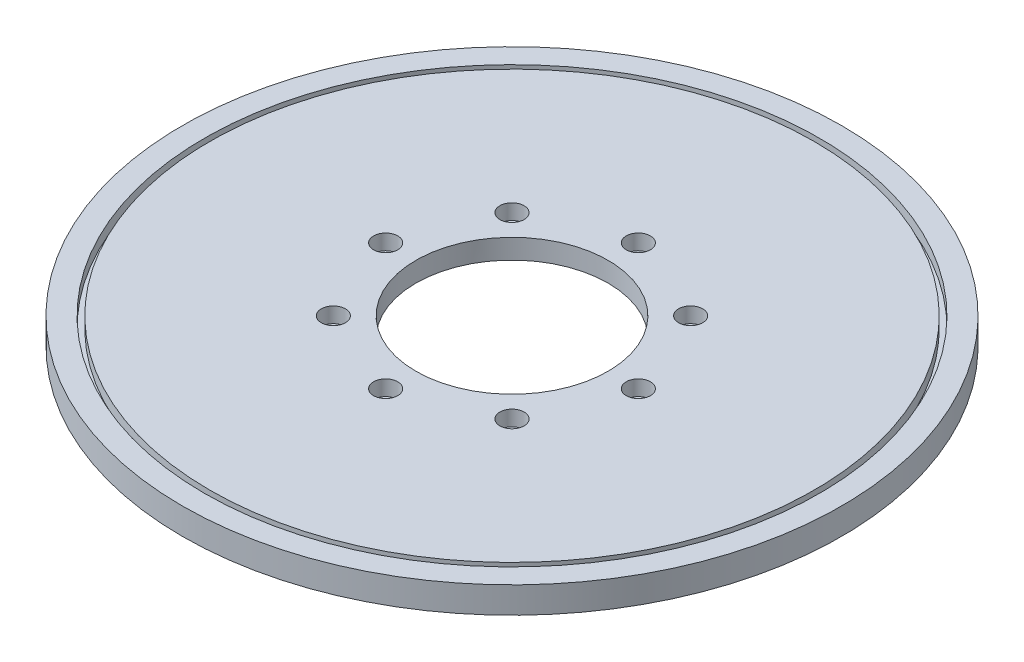
SolidWorks part; units mm, degrees
ref_plane "Front Plane" through (0, 0, 0) normal (0, 0, 1) x (1, 0, 0)
ref_plane "Top Plane" through (0, 0, 0) normal (0, 1, 0) x (1, 0, 0)
ref_plane "Right Plane" through (0, 0, 0) normal (1, 0, 0) x (0, 0, -1)
sketch "Sketch1" plane through (0, 0, 0) normal (0, 1, 0) x (1, 0, 0)
  circle A0 centre (0, 0) radius 300
  point P0 (0, 0)
  dimension "D1" = 600
extrude "plate" add sketch "Sketch1" along normal blind 24
sketch "Sketch2" plane through (0, 24, 0) normal (0, 1, 0) x (1, 0, 0)
  circle A0 centre (0, 0) radius 87.5
  dimension "D1" = 175
extrude "bearing-hole" cut sketch "Sketch2" against normal through all
sketch "Sketch4" plane through (0, 24, 0) normal (0, 1, 0) x (1, 0, 0)
  circle A0 centre (0, 0) radius 280
  circle A1 centre (0, 0) radius 275
  point P0 (0, 0)
  point P6 (0, 0)
  dimension "D1" = 560
  dimension "D2" = 550
extrude "Cut-Extrude3" cut sketch "Sketch4" against normal blind 10
sketch "Sketch5" plane through (0, 0, 0) normal (0, -1, 0) x (1, 0, 0)
  circle A0 centre (0, 0) radius 135
  dimension "D1" = 270
extrude "Cut-Extrude4" cut sketch "Sketch5" against normal blind 6
sketch "Sketch6" plane through (0, 6, 0) normal (0, -1, 0) x (1, 0, 0)
  circle A0 centre (0, 115) radius 6
  circle A1 centre (81.3173, 81.3173) radius 6
  circle A2 centre (115, 0) radius 6
  circle A3 centre (81.3173, -81.3173) radius 6
  circle A4 centre (0, -115) radius 6
  circle A5 centre (-81.3173, -81.3173) radius 6
  circle A6 centre (-115, 0) radius 6
  circle A7 centre (-81.3173, 81.3173) radius 6
  point P2 (0, 0)
  point P19 (0, 0)
  dimension "D1" = 12
  dimension "D2" = 115
  dimension "D3" = 8
extrude "Cut-Extrude5" cut sketch "Sketch6" against normal through all
sketch "Sketch7" plane through (0, 24, 0) normal (0, 1, 0) x (1, 0, 0)
  circle A0 centre (0, 115) radius 11
  circle A1 centre (81.3173, 81.3173) radius 11
  circle A2 centre (115, 0) radius 11
  circle A3 centre (81.3173, -81.3173) radius 11
  circle A4 centre (0, -115) radius 11
  circle A5 centre (-81.3173, -81.3173) radius 11
  circle A6 centre (-115, 0) radius 11
  circle A7 centre (-81.3173, 81.3173) radius 11
  point P19 (0, 0)
  dimension "D1" = 22
  dimension "D2" = 8
extrude "Cut-Extrude6" cut sketch "Sketch7" against normal blind 14
